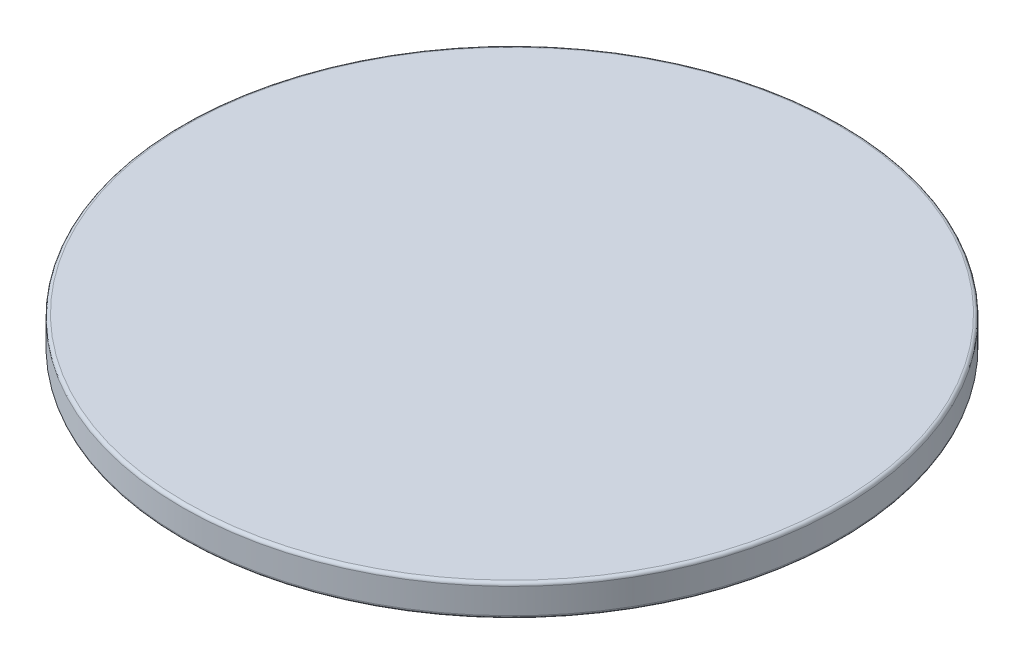
SolidWorks part; units mm, degrees
ref_plane "Front" through (0, 0, 0) normal (0, 0, 1) x (1, 0, 0)
ref_plane "Top" through (0, 0, 0) normal (0, 1, 0) x (1, 0, 0)
ref_plane "Right" through (0, 0, 0) normal (1, 0, 0) x (0, 0, -1)
sketch "Sketch2" plane through (0, 0, 0) normal (0, 1, 0) x (1, 0, 0)
  circle A0 centre (0, 0) radius 66.04
  dimension "D1" = 132.08
extrude "Boss-Extrude1" add sketch "Sketch2" along normal blind 6.35
fillet "Fillet1" radius 0.635 2 edges at (0, 0, 66.04) (0, 6.35, 66.04)
